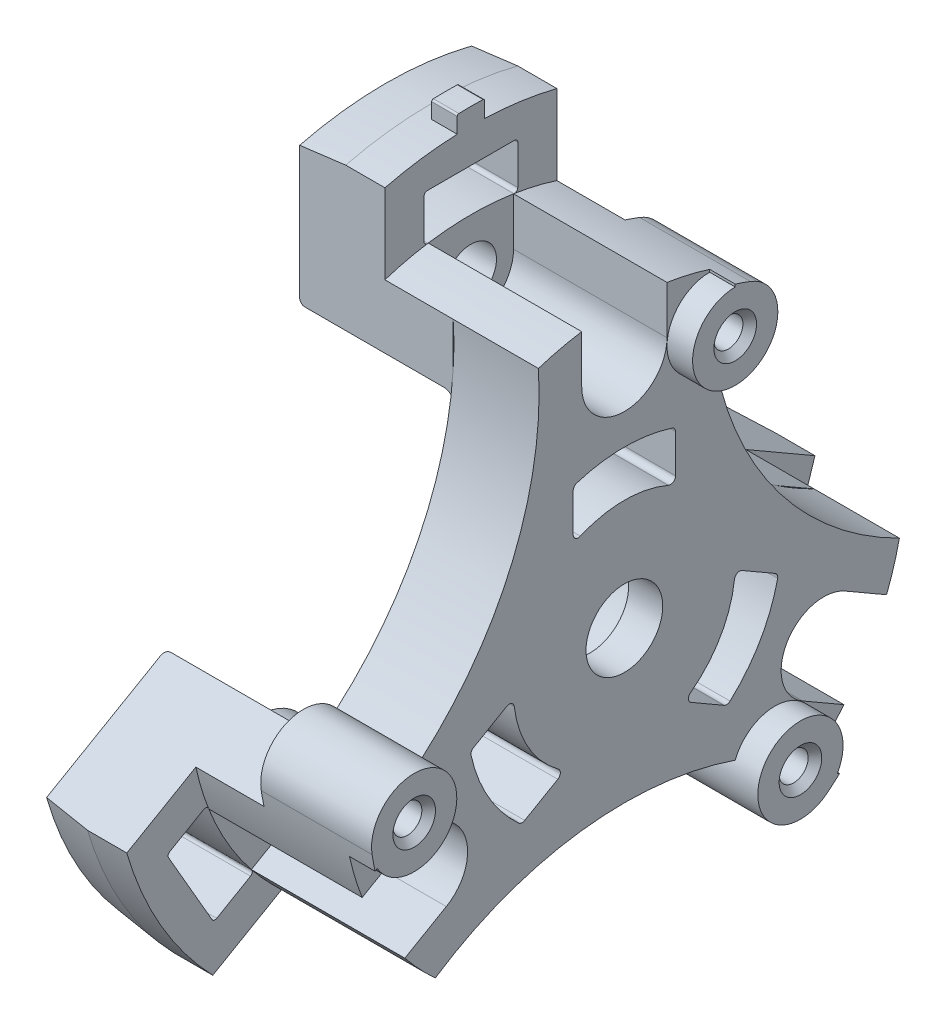
SolidWorks part; units mm, degrees
ref_plane "Front" through (0, 0, 0) normal (0, 0, 1) x (1, 0, 0)
ref_plane "Top" through (0, 0, 0) normal (0, 1, 0) x (1, 0, 0)
ref_plane "Right" through (0, 0, 0) normal (1, 0, 0) x (0, 0, -1)
sketch "草图1" plane through (0, 0, 0) normal (0, 0, 1) x (1, 0, 0)
  line L0 (-65.7429, 0) -> (89.5714, 0) construction
  line L1 (0, 67.1143) -> (0, -71.9143) construction
  line L2 (-7, 6.5) -> (-5, 6.5)
  line L3 (-5, 6.5) -> (-5, 16.5)
  line L4 (-5, 16.5) -> (0, 16.5)
  line L5 (0, 16.5) -> (0, 2.25)
  line L6 (-2, 4) -> (-7, 4)
  line L7 (-7, 4) -> (-7, 6.5)
  line L8 (-2, 4) -> (-2, 2.25)
  line L9 (-2, 2.25) -> (0, 2.25)
  dimension "D1" = 4.5
  dimension "D2" = 5
  dimension "D3" = 8
  dimension "D4" = 7
  dimension "D5" = 5
  dimension "D6" = 13
  dimension "D7" = 33
  dimension "D8" = 2
revolve "旋转1" add sketch "草图1" angle 360 about L0
sketch "草图2" plane through (-5, 0, 0) normal (-1, 0, 0) x (0, 0, 1)
  line L0 (-23.9515, 0) -> (26.381, 0) construction
  line L1 (0, 44.3891) -> (0, -20.5254) construction
  line L2 (0, 0) -> (-21.2641, -12.2768) construction
  line L3 (0, 0) -> (20.7932, -12.005) construction
  line L4 (0, 0) -> (-61.1055, 35.2793) construction
  line L5 (-5, 31.2128) -> (-5, 9) construction
  line L6 (5, 31.2128) -> (5, 9) construction
  circle A1 centre (-25, 14.4338) radius 20
  point P7 (0, 9)
  point P9 (-7.6795, 4.4338)
  dimension "D6" = 40
  dimension "D1" = 120
  dimension "D2" = 120
  dimension "D3" = 9
  dimension "D5" = 60
  dimension "D7" = 10
extrude "切除-拉伸1" cut sketch "草图2" against normal blind 10 contours A1
pattern_circular "阵列(圆周)1" count 3 over 360 about axis through (0, 0, 0) along (1, 0, 0) of "切除-拉伸1"
sketch "草图3" plane through (-5, 0, 0) normal (-1, 0, 0) x (0, 0, 1)
  line L0 (0, 18) -> (0, -12.9057) construction
  line L1 (-20.442, 0) -> (20.8303, 0) construction
  line L2 (-3, 8.4806) -> (-3, 6.241)
  line L4 (3, 8.4806) -> (3, 6.241)
  arc A0 (2.791, 8.7664) -> (-2.791, 8.7664) centre (0, 0) ccw
  circle A1 centre (0, 0) radius 6.5 construction
  arc A2 (2.5809, 5.9657) -> (-2.5809, 5.9657) centre (0, 0) ccw
  arc A3 (3, 6.241) -> (2.5809, 5.9657) centre (2.7, 6.241) cw
  arc A4 (-2.5809, 5.9657) -> (-3, 6.241) centre (-2.7, 6.241) cw
  arc A5 (3, 8.4806) -> (2.791, 8.7664) centre (2.7, 8.4806) ccw
  arc A6 (-2.791, 8.7664) -> (-3, 8.4806) centre (-2.7, 8.4806) ccw
  point P11 (3, 5.7663)
  point P16 (-3, 5.7663)
  point P19 (3, 8.6971)
  point P22 (-3, 8.6971)
  dimension "D1" = 9.2
  dimension "D3" = 0.3
  dimension "D2" = 6
extrude "切除-拉伸2" cut sketch "草图3" against normal blind 10
pattern_circular "阵列(圆周)2" count 3 over 360 about axis through (0, 0, 0) along (1, 0, 0) of "切除-拉伸2"
sketch "草图4" plane through (-5, 0, 0) normal (-1, 0, 0) x (0, 0, 1)
  line L0 (-16.7535, 0) -> (15.8993, 0) construction
  line L1 (0, 19.3876) -> (0, -16.6742) construction
  line L2 (-5.0408, 15.7111) -> (-5.0408, 11.9829)
  line L4 (5.0408, 11.9829) -> (5.0408, 15.7111)
  circle A0 centre (0, 0) radius 13.5 construction
  arc A1 (5.0408, 15.7111) -> (-5.0408, 15.7111) centre (0, 0) ccw construction
  arc A2 (5.0408, 15.7111) -> (-5.0408, 15.7111) centre (0, 0) ccw
  circle A3 centre (0, 13.5) radius 1.5
  arc A4 (-3.128, 12.6181) -> (3.128, 12.6181) centre (0, 13.5) ccw
  arc A5 (-3.128, 12.6181) -> (-5.0408, 11.9829) centre (0, 0) ccw
  arc A6 (5.0408, 11.9829) -> (3.128, 12.6181) centre (0, 0) ccw
  dimension "D1" = 27
  dimension "D2" = 3
  dimension "D4" = 6.5
  dimension "D5" = 26
  dimension "D3" = 10.0817
extrude "凸台-拉伸1" add sketch "草图4" along normal blind 9
pattern_circular "阵列(圆周)3" count 3 over 360 about axis through (0, 0, 0) along (1, 0, 0) of "凸台-拉伸1"
sketch "草图5" plane through (-14, 0, 0) normal (-1, 0, 0) x (0, 0, 1)
  line L0 (-16.1323, 0) -> (16.637, 0) construction
  line L1 (0, 17.8058) -> (0, -12.3621) construction
  line L3 (-3.25, 12.5872) -> (-3.25, 9.2908)
  line L4 (-3.25, 9.2908) -> (3.25, 9.2908)
  line L5 (3.25, 12.5872) -> (3.25, 9.2908)
  arc A2 (3.25, 12.5872) -> (-3.25, 12.5872) centre (0, 0) ccw
  point P10 (0, 9.2908)
  point P11 (0, 13.55)
  dimension "D1" = 6.5
  dimension "D2" = 26
extrude "切除-拉伸3" cut sketch "草图5" against normal blind 1.7 contours L4 L5 A2 L3
sketch "草图10" plane through (-5, 0, 0) normal (-1, 0, 0) x (0, 0, 1)
  point P1 (0, 0)
  dimension "D1" = 12.8775
sketch "草图16" plane through (-12.3, 0, 0) normal (-1, 0, 0) x (0, 0, 1)
  line L0 (0, 19.1849) -> (0, -11.6277) construction
  line L1 (-18.1803, 0) -> (19.4691, 0) construction
  arc A0 (-2.5906, 12.7393) -> (2.5906, 12.7393) centre (0, 13.5) ccw
  arc A1 (-3.128, 12.6181) -> (3.128, 12.6181) centre (0, 13.5) ccw construction
  arc A2 (-3.128, 12.6181) -> (3.128, 12.6181) centre (0, 13.5) ccw
  arc A3 (-1.3858, 12.9259) -> (-3.128, 12.6181) centre (0, 0) ccw construction
  arc A4 (-2.5906, 12.7393) -> (-3.128, 12.6181) centre (0, 0) ccw
  arc A5 (5.0408, 11.9829) -> (1.3858, 12.9259) centre (0, 0) ccw construction
  arc A6 (3.128, 12.6181) -> (2.5906, 12.7393) centre (0, 0) ccw
  dimension "D1" = 5.4
extrude "切除-拉伸8" cut sketch "草图16" against normal blind 2.5 contours A2 A6 A0 A4
pattern_circular "阵列(圆周)4" count 3 over 360 about axis through (0, 0, 0) along (1, 0, 0) of "切除-拉伸3", "切除-拉伸8"
sketch "草图6" plane through (0, 0, 0) normal (1, 0, 0) x (0, 0, -1)
  line L0 (-17.245, 0) -> (20.4566, 0) construction
  line L1 (0, 20.1005) -> (0, -14.3306) construction
  line L2 (-2.5, 16.3095) -> (-2.5, 13.5)
  line L3 (2.5, 16.3095) -> (2.5, 13.5)
  circle A0 centre (0, 0) radius 13.5 construction
  arc A1 (5.0408, 15.7111) -> (-5.0408, 15.7111) centre (0, 0) ccw construction
  arc A3 (2.5, 16.3095) -> (-2.5, 16.3095) centre (0, 0) ccw
  arc A4 (-2.5, 13.5) -> (2.5, 13.5) centre (0, 13.5) ccw
  dimension "D1" = 27
  dimension "D3" = 5
  dimension "D2" = 5
extrude "切除-拉伸4" cut sketch "草图6" against normal blind 9
pattern_circular "阵列(圆周)5" count 3 over 360 about axis through (0, 0, 0) along (1, 0, 0) of "切除-拉伸4"
sketch "草图7" plane through (-5, 0, 0) normal (-1, 0, 0) x (0, 0, 1)
  line L0 (0, 19.1221) -> (0, -13.8647) construction
  line L1 (16.0973, 0) -> (-17.961, 0) construction
  line L2 (-5, 15.5767) -> (-5, 15.7242)
  arc A1 (-5.8929, 15.4118) -> (-5, 15.5767) centre (-5, 13.0767) ccw
  circle A5 centre (0, 0) radius 14 construction
  arc A6 (-2.5, 16.3095) -> (-5.0408, 15.7111) centre (0, 0) ccw construction
  arc A7 (-5, 15.7242) -> (-5.8929, 15.4118) centre (0, 0) ccw
  point P7 (-5, 13.0767)
  dimension "D1" = 28
  dimension "D3" = 5
  dimension "D2" = 5
extrude "凸台-拉伸2" add sketch "草图7" against normal blind 6.5 contours A1 L2 A7
sketch "草图9" plane through (1.5, 0, 0) normal (1, 0, 0) x (0, 0, -1)
  line L0 (0, 17.5729) -> (0, -10.6538) construction
  line L1 (-14.0745, 0) -> (16.4041, 0) construction
  circle A0 centre (0, 0) radius 14 construction
  circle A1 centre (5, 13.0767) radius 0.85
  dimension "D1" = 1.7
extrude "切除-拉伸7" cut sketch "草图9" against normal blind 6.4 contours A1
chamfer "倒角3" distance 0.4 angle 45 1 edges at (1.5, 13.0767, -5.85)
pattern_circular "阵列(圆周)8" count 3 over 360 about axis through (0, 0, 0) along (1, 0, 0) of "凸台-拉伸2", "切除-拉伸7", "倒角3"
chamfer "倒角4" distance 0.35 angle 60 1 edges at (-7, 0, 4)
fillet "圆角6" radius 0.5 9 edges at (-5, 12.3376, -4.0968) (-5, 10.25, 0) (-5, 12.3376, 4.0968) (-5, -9.7167, -8.6363) (-5, -5.125, -8.8768) (-5, -2.6209, -12.7331) (-5, -2.6209, 12.7331) (-5, -5.125, 8.8768) (-5, -9.7167, 8.6363)
fillet "圆角7" radius 0.5 1 edges at (-7, 0, 6.5)
sketch "草图11" plane through (-14, 0, 0) normal (-1, 0, 0) x (0, 0, 1)
  line L0 (-24.0343, 0) -> (27.0991, 0) construction
  line L1 (0, 23.8854) -> (0, -19.7008) construction
  line L2 (-5.0408, 15.7111) -> (-5.0408, 20.386)
  line L3 (5.0408, 15.7111) -> (5.0408, 20.386)
  line L4 (-2.55, 19) -> (2.55, 19)
  line L5 (-2.75, 18.8) -> (-2.75, 16.2692)
  line L7 (2.75, 18.8) -> (2.75, 16.2692)
  arc A0 (5.0408, 20.386) -> (0, 21) centre (0, 0) ccw
  arc A1 (5.0408, 15.7111) -> (-5.0408, 15.7111) centre (0, 0) ccw construction
  arc A2 (5.0408, 15.7111) -> (2.75, 16.2692) centre (0, 0) ccw
  arc A3 (-2.75, 16.2692) -> (-5.0408, 15.7111) centre (0, 0) ccw
  arc A4 (0, 21) -> (-5.0408, 20.386) centre (0, 0) ccw
  arc A5 (2.75, 18.8) -> (2.55, 19) centre (2.55, 18.8) ccw
  arc A6 (-2.75, 18.8) -> (-2.55, 19) centre (-2.55, 18.8) cw
  point P15 (0, 17)
  point P16 (0, 19)
  point P18 (2.75, 19)
  point P20 (0, 22)
  point P23 (-2.75, 19)
  dimension "D1" = 42
  dimension "D4" = 0.2
  dimension "D2" = 5.5
  dimension "D3" = 19
extrude "凸台-拉伸3" add sketch "草图11" against normal up to surface (5 mm away) up to face at (-9, 13.5, -1.5)
pattern_circular "阵列(圆周)9" count 3 over 360 about axis through (0, 0, 0) along (1, 0, 0) of "凸台-拉伸3"
sketch "草图12" plane through (-9, 0, 0) normal (1, 0, 0) x (0, 0, -1)
  line L0 (0, 23.0537) -> (0, -15.9342) construction
  line L1 (-23.5138, 0) -> (22.1093, 0) construction
  line L2 (-0.8, 21.8888) -> (-0.8, 20.9848)
  line L3 (0.8, 21.8888) -> (0.8, 20.9848)
  arc A0 (0.7032, 21.9888) -> (-0.7032, 21.9888) centre (0, 0) ccw
  arc A1 (5.0408, 20.386) -> (-5.0408, 20.386) centre (0, 0) ccw construction
  arc A2 (0.8, 20.9848) -> (-0.8, 20.9848) centre (0, 0) ccw
  arc A3 (-22, 0) -> (22, 0) centre (0, 0) ccw
  arc A4 (-0.8, 21.8888) -> (-0.7032, 21.9888) centre (-0.7, 21.8888) cw
  arc A5 (0.7032, 21.9888) -> (0.8, 21.8888) centre (0.7, 21.8888) cw
  dimension "D2" = 1
  dimension "D3" = 0.1
  dimension "D1" = 1.6
extrude "凸台-拉伸4" add sketch "草图12" against normal blind 1.5 contours A0 A4 L2 A2 L3 A5
pattern_circular "阵列(圆周)10" [suppressed] count 3 over 360
fillet "圆角9" radius 0.3 6 edges at (-14, 12.5878, -3.2477) (-14, 12.5878, 3.2477) (-14, -9.1065, -9.2775) (-14, -3.4813, -12.5252) (-14, -3.4813, 12.5252) (-14, -9.1065, 9.2775)
fillet "圆角10" radius 0.2 6 edges at (-11.5, 16.2692, -2.75) (-11.5, 16.2692, 2.75) (-11.5, -10.5162, -12.7146) (-11.5, -5.753, -15.4646) (-11.5, -5.753, 15.4646) (-11.5, -10.5162, 12.7146)
sketch "草图14" plane through (0, 0, 0) normal (0, 0, 1) x (1, 0, 0)
  line L0 (6.5511, 0) -> (-13.5644, 0) construction
  line L1 (-11.2016, 4) -> (3.5999, 4) construction
  line L2 (-7.4213, 4.75) -> (-6.809, 4.75)
  line L3 (-6.809, 4.75) -> (-6.134, 4.075)
  line L4 (-6.134, 4.075) -> (-2.6377, 4.075)
  line L5 (-2.6377, 4.075) -> (-2.6377, 4)
  line L6 (-2.6377, 4) -> (-7.4213, 4)
  line L7 (-7.4213, 4) -> (-7.4213, 4.75)
  dimension "D1" = 4
  dimension "D2" = 0.15
  dimension "D3" = 1.5
  dimension "D4" = 45
revolve "切除-旋转1" [suppressed] cut sketch "草图14" angle 360 about L1
pattern_circular "阵列(圆周)11" [suppressed] count 4 over 360
sketch "草图15" plane through (0, 0, 0) normal (0, 0, 1) x (1, 0, 0)
  line L0 (8.389, 0) -> (-25.6839, 0) construction
  line L1 (0, 24.288) -> (0, -16.6697) construction
  line L2 (-11.3, 22.5255) -> (-11.3, 9.7426) construction
  line L4 (-14, 12.3077) -> (-14, 20.386) construction
  line L5 (-16.1078, 21) -> (-11.3, 21)
  line L6 (-11.3, 21) -> (-16.1078, 20.4097)
  line L7 (-16.1078, 20.4097) -> (-16.1078, 21)
  dimension "D1" = 2.7
  dimension "D2" = 21
  dimension "D3" = 7
revolve "切除-旋转2" cut sketch "草图15" angle 360 about L0
fillet "圆角11" radius 0.2 3 edges at (-9.8, 10.8, 0) (-9.8, -5.4, -9.3531) (-9.8, -5.4, 9.3531)
